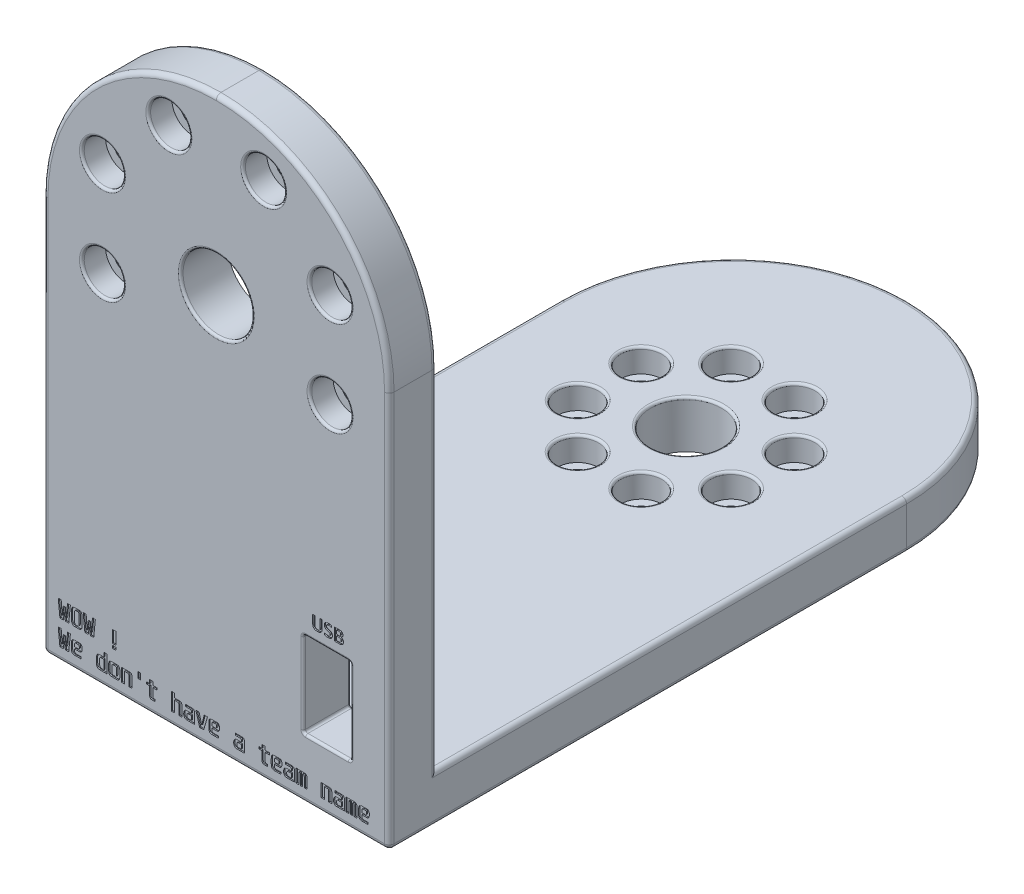
SolidWorks part; units mm, degrees
ref_plane "Front Plane" through (0, 0, 0) normal (0, 0, 1) x (1, 0, 0)
ref_plane "Top Plane" through (0, 0, 0) normal (0, 1, 0) x (1, 0, 0)
ref_plane "Right Plane" through (0, 0, 0) normal (1, 0, 0) x (0, 0, -1)
sketch "Sketch1" plane through (0, 0, 0) normal (1, 0, 0) x (0, 0, -1)
  line L1 (-80.0483, 57.0999) -> (-70.0483, 57.0999)
  line L2 (-80.0483, 57.0999) -> (-80.0483, -62.9001)
  line L3 (-80.0483, -62.9001) -> (-70.0483, -62.9001)
  line L4 (-70.0483, 57.0999) -> (-70.0483, -52.9001)
  line L7 (-70.0483, -62.9001) -> (65.5517, -62.9001)
  line L9 (-70.0483, -52.9001) -> (65.5517, -52.9001)
  line L10 (65.5517, -62.9001) -> (65.5517, -52.9001)
  point P0 (-75.0483, -2.9001)
  dimension "D1" = 120
  dimension "D2" = 10
  dimension "D3" = 10
  dimension "D4" = 135.6
extrude "Boss-Extrude1" add sketch "Sketch1" along normal mid plane 73
fillet "Fillet1" radius 36.5 2 edges at (-36.5, 57.0999, 75.0483) (36.5, 57.0999, 75.0483)
sketch "Sketch2" plane through (0, 0, 80.0483) normal (0, 0, 1) x (1, 0, 0)
  line L0 (0, 60.3729) -> (0, -70.6367) construction
  line L1 (-24, 55.128) -> (-24, -14.8404) construction
  circle A0 centre (0, 20.5999) radius 7.5
  circle A1 centre (-10, 46.5999) radius 2.575
  circle A2 centre (-24, 32.5999) radius 2.575
  circle A3 centre (-24, 12.5999) radius 2.575
  circle A4 centre (24, 12.5999) radius 2.575
  circle A5 centre (10, 46.5999) radius 2.575
  circle A6 centre (24, 32.5999) radius 2.575
  point P12 (-24, 6.7415)
  point P15 (-24, 28.0334)
  dimension "D1" = 15
  dimension "D3" = 5.15
  dimension "D4" = 24
  dimension "D7" = 2
  dimension "D2" = 36.5
  dimension "D5" = 14
  dimension "D6" = 10
  dimension "D8" = 20
  dimension "D9" = 26
extrude "Cut-Extrude1" cut sketch "Sketch2" against normal blind 10
sketch "Sketch3" plane through (0, 0, 80.0483) normal (0, 0, 1) x (1, 0, 0)
  circle A2 centre (-24, 12.5999) radius 4.35
  circle A4 centre (-24, 32.5999) radius 4.35
  circle A6 centre (-10, 46.5999) radius 4.35
  circle A10 centre (24, 32.5999) radius 4.35
  circle A12 centre (10, 46.5999) radius 4.35
  circle A14 centre (24, 12.5999) radius 4.35
  dimension "D1" = 8.7
extrude "Cut-Extrude3" cut sketch "Sketch3" against normal blind 5
sketch "Sketch5" plane through (0, -52.9001, 0) normal (0, 1, 0) x (1, 0, 0)
  line L0 (-56.4985, 19.0517) -> (56.4985, 19.0517) construction
  line L1 (0, 97.2592) -> (0, -89.7316) construction
  circle A0 centre (-6.697, 35.2195) radius 2.575
  circle A1 centre (6.697, 35.2195) radius 2.575
  circle A2 centre (16.1679, 25.7486) radius 2.575
  circle A3 centre (16.1679, 12.3547) radius 2.575
  circle A4 centre (6.697, 2.8838) radius 2.575
  circle A5 centre (-6.697, 2.8838) radius 2.575
  circle A6 centre (-16.1679, 12.3547) radius 2.575
  circle A7 centre (-16.1679, 25.7486) radius 2.575
  circle A8 centre (0, 19.0517) radius 7.5
  point P9 (0, 19.0517)
  point P24 (0, 19.0517)
  dimension "D2" = 5.15
  dimension "D5" = 15
  dimension "D1" = 99.1
  dimension "D4" = 35
  dimension "D3" = 8
extrude "Cut-Extrude4" cut sketch "Sketch5" against normal blind 10
sketch "Sketch6" plane through (0, -52.9001, 0) normal (0, 1, 0) x (1, 0, 0)
  circle A2 centre (16.1679, 12.3547) radius 4.35
  circle A4 centre (16.1679, 25.7486) radius 4.35
  circle A6 centre (6.697, 35.2195) radius 4.35
  circle A8 centre (-6.697, 35.2195) radius 4.35
  circle A10 centre (-16.1679, 25.7486) radius 4.35
  circle A12 centre (-16.1679, 12.3547) radius 4.35
  circle A14 centre (-6.697, 2.8838) radius 4.35
  circle A16 centre (6.697, 2.8838) radius 4.35
  dimension "D1" = 8.7
extrude "Cut-Extrude5" cut sketch "Sketch6" against normal blind 5
sketch "Sketch7" plane through (0, 0, 80.0483) normal (0, 0, 1) x (1, 0, 0)
  line L1 (18.3445, -32.3199) -> (28.3445, -32.3199)
  line L2 (18.3445, -32.3199) -> (18.3445, -50.3199)
  line L3 (18.3445, -50.3199) -> (28.3445, -50.3199)
  line L4 (28.3445, -32.3199) -> (28.3445, -50.3199)
  line L5 (18.3445, -32.3199) -> (28.3445, -50.3199) construction
  line L6 (18.3445, -50.3199) -> (28.3445, -32.3199) construction
  point P0 (23.3445, -41.3199)
  dimension "D1" = 18
  dimension "D2" = 10
extrude "Cut-Extrude6" cut sketch "Sketch7" against normal blind 10
fillet "Fillet2" radius 36.5 2 edges at (-36.5, -57.9001, -65.5517) (36.5, -57.9001, -65.5517)
fillet "Fillet3" radius 1 17 edges at (-36.5, -62.9001, 25.4983) (-25.8094, -62.9001, -54.8611) (25.8094, -62.9001, -54.8611) (-36.5, -52.9001, 20.4983) (-25.8094, -52.9001, -54.8611) (25.8094, -52.9001, -54.8611) (-36.5, -16.1501, 70.0483) (-25.8094, 46.4093, 70.0483) (36.5, -16.1501, 70.0483) (36.5, -21.1501, 80.0483) (-36.5, -21.1501, 80.0483) (-25.8094, 46.4093, 80.0483) (0, -62.9001, 80.0483) (36.5, -62.9001, 25.4983) (36.5, -52.9001, 20.4983) (25.8094, 46.4093, 70.0483) (25.8094, 46.4093, 80.0483)
fillet "Fillet4" radius 0.5 19 edges at (-5.65, 46.5999, 80.0483) (28.35, 32.5999, 80.0483) (14.35, 46.5999, 80.0483) (28.35, 12.5999, 80.0483) (7.5, 20.5999, 80.0483) (-19.65, 12.5999, 80.0483) (-19.65, 32.5999, 80.0483) (28.3445, -32.3199, 75.0483) (28.3445, -50.3199, 75.0483) (18.3445, -32.3199, 75.0483) (18.3445, -50.3199, 75.0483) (23.3445, -50.3199, 70.0483) (28.3445, -41.3199, 70.0483) (18.3445, -41.3199, 70.0483) (23.3445, -32.3199, 70.0483) (28.3445, -41.3199, 80.0483) (23.3445, -32.3199, 80.0483) (23.3445, -50.3199, 80.0483) (18.3445, -41.3199, 80.0483)
fillet "Fillet5" radius 0.5 9 edges at (0, -52.9001, -11.5517) (16.1679, -52.9001, -8.0047) (16.1679, -52.9001, -21.3986) (6.697, -52.9001, -30.8695) (-6.697, -52.9001, -30.8695) (-16.1679, -52.9001, -21.3986) (-6.697, -52.9001, 1.4662) (6.697, -52.9001, 1.4662) (-16.1679, -52.9001, -8.0047)
sketch "Sketch8" plane through (0, 0, 80.0483) normal (0, 0, 1) x (1, 0, 0)
  line L0 (18.9589, -30.3144) -> (27.7301, -30.3144) construction
  line L1 (23.3445, -55.0157) -> (23.3445, -16.4239) construction
  line L2 (27.8445, -50.8199) -> (18.8445, -50.8199) construction
  text T0 "<b>USB</b>" font ".Apple SD Gothic NeoI" height in points 8
  point P5 (23.3445, -30.3144)
  point P8 (23.3445, -50.8199)
  point P9 (30.2534, -29.0536)
  dimension "D1" = 8.7712
extrude "Cut-Extrude7" cut sketch "Sketch8" against normal blind 0.25
sketch "Sketch9" plane through (0, 0, 80.0483) normal (0, 0, 1) x (1, 0, 0)
  line L0 (-33.3661, -54.9021) -> (33.3661, -54.9021) construction
  text T0 "<b>WOW !</b>\r\n<b>We don't have a team name</b>" font "Unispace" height 3.4717
  point P2 (0, 0)
  point P3 (-21.7605, -14.1709)
  point P4 (-24.5503, -13.9477)
  point P5 (-26.2242, -14.2825)
  point P7 (0, -54.9021)
  point P8 (0, 0)
  point P9 (-26.6706, -7.5869)
  point P10 (-31.8038, -6.8058)
  point P12 (0, 0)
  point P13 (-33.9241, -7.9217)
  point P14 (-34.2589, -8.1449)
  point P15 (-34.8168, -8.1449)
  point P16 (-33.8125, -54.3442)
  point P17 (-33.3661, -54.9021)
extrude "Cut-Extrude8" cut sketch "Sketch9" against normal blind 0.25
